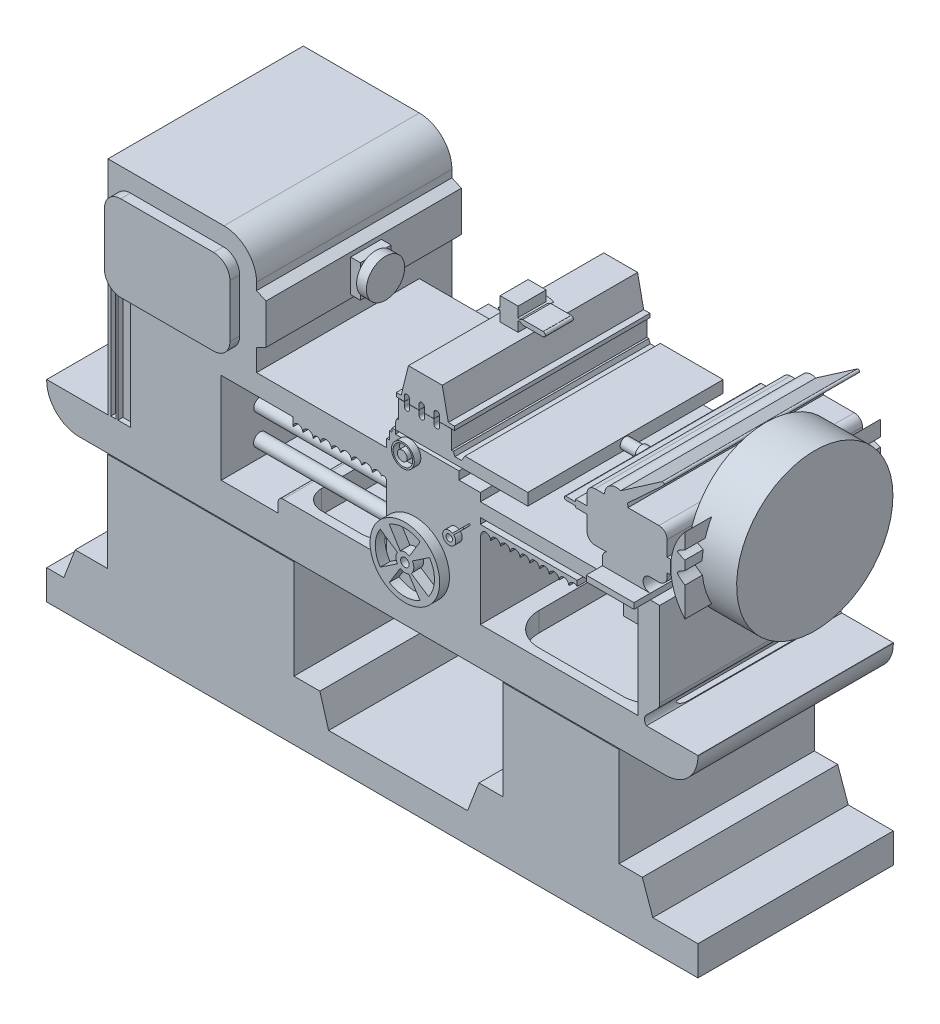
SolidWorks part; units mm, degrees
ref_plane "Front Plane" through (0, 0, 0) normal (0, 0, 1) x (1, 0, 0)
ref_plane "Top Plane" through (0, 0, 0) normal (0, 1, 0) x (1, 0, 0)
ref_plane "Right Plane" through (0, 0, 0) normal (1, 0, 0) x (0, 0, -1)
sketch "Sketch1" plane through (0, 0, 0) normal (0, 0, 1) x (1, 0, 0)
  line L0 (0, 100.2969) -> (0, -49.7031) construction
  line L1 (0, 25.2969) -> (-100, 25.2969) construction
  line L2 (0, 25.2969) -> (100, 25.2969) construction
  line L3 (-94.7329, 25.2969) -> (-91.2441, 34.4213)
  line L4 (-100, 25.2969) -> (100, 25.2969)
  line L5 (-100, 25.2969) -> (-100, 16.1725)
  line L6 (-100, 16.1725) -> (100, 16.1725)
  line L7 (100, 25.2969) -> (100, 16.1725)
  line L8 (-91.2441, 34.4213) -> (-16.1019, 34.4213)
  line L9 (-16.1019, 34.4213) -> (-13.4183, 25.2969)
  line L10 (-13.4183, 25.2969) -> (-94.7329, 25.2969)
  line L11 (29.2518, 25.2969) -> (32.7405, 34.4213)
  line L12 (32.7405, 34.4213) -> (82.9248, 34.4213)
  line L13 (82.9248, 34.4213) -> (86.1452, 25.2969)
  line L14 (86.1452, 25.2969) -> (29.2518, 25.2969)
extrude "Boss-Extrude5" add sketch "Sketch1" against normal blind 60 contours L7 L4 L5 L6 | L9 L8 L3 L4 | L12 L13 L14 L11 region at (0, 20.7347, 0) region at (-53.8769, 29.7991, 0)
sketch "Sketch5" plane through (0, 0, 0) normal (0, 0, 1) x (1, 0, 0)
  line L0 (-91.2441, 34.4213) -> (-16.1019, 34.4213) construction
  line L1 (-81.2902, 34.4213) -> (-24.0553, 34.4213)
  line L2 (-81.2902, 34.4213) -> (-81.2902, 64.836)
  line L3 (-81.2902, 64.836) -> (-24.0553, 64.836)
  line L4 (-24.0553, 34.4213) -> (-24.0553, 64.836)
  line L5 (32.7405, 34.4213) -> (82.9248, 34.4213) construction
  line L6 (40.0921, 34.4213) -> (75.7603, 34.4213)
  line L7 (40.0921, 34.4213) -> (40.0921, 64.836)
  line L8 (40.0921, 64.836) -> (75.7603, 64.836)
  line L9 (75.7603, 34.4213) -> (75.7603, 64.836)
extrude "Boss-Extrude6" add sketch "Sketch5" against normal blind 60
sketch "Sketch6" plane through (0, 0, 0) normal (0, 0, 1) x (1, 0, 0)
  line L0 (-90, 65.1125) -> (90, 65.1125)
  line L1 (100, 75.1125) -> (100, 75.3429)
  line L2 (100, 75.3429) -> (-100, 75.3429)
  line L3 (-100, 75.3429) -> (-100, 75.1125)
  arc A0 (100, 75.1125) -> (90, 65.1125) centre (90, 75.1125) cw
  arc A1 (-90, 65.1125) -> (-100, 75.1125) centre (-90, 75.1125) cw
  dimension "D1" = 10
extrude "Boss-Extrude7" add sketch "Sketch6" against normal blind 60 separate body
sketch "Sketch7" plane through (0, 0, 0) normal (0, 0, 1) x (1, 0, 0)
  line L0 (100, 75.3429) -> (-100, 75.3429) construction
  line L1 (-81.1767, 75.3429) -> (-35.5534, 75.3429)
  line L2 (-81.1767, 75.3429) -> (-81.1767, 143.4491)
  line L3 (-81.1767, 143.4491) -> (-45.5534, 143.4491)
  line L4 (-35.5534, 75.3429) -> (-35.5534, 133.4491)
  arc A0 (-35.5534, 133.4491) -> (-45.5534, 143.4491) centre (-45.5534, 133.4491) ccw
  dimension "D1" = 10
extrude "Boss-Extrude8" add sketch "Sketch7" against normal blind 60
sketch "Sketch8" plane through (0, 0, 0) normal (0, 0, 1) x (1, 0, 0)
  line L0 (-35.5534, 75.3429) -> (-35.5534, 133.4491) construction
  line L1 (-81.1767, 75.3429) -> (-35.5534, 75.3429)
  line L2 (-81.1767, 75.3429) -> (-81.1767, 109.1187)
  line L3 (-81.1767, 109.1187) -> (-35.5534, 109.1187)
  line L4 (-35.5534, 75.3429) -> (-35.5534, 109.1187)
extrude "Cut-Extrude2" cut sketch "Sketch8" against normal blind 50
sketch "Sketch9" plane through (0, 0, -50) normal (0, 0, 1) x (1, 0, 0)
  line L0 (-35.5534, 109.1187) -> (-81.1767, 109.1187) construction
  line L1 (-81.1767, 75.3429) -> (-77.563, 75.3429)
  line L2 (-81.1767, 75.3429) -> (-81.1767, 109.1187)
  line L3 (-81.1767, 109.1187) -> (-77.563, 109.1187)
  line L4 (-77.563, 75.3429) -> (-77.563, 109.1187)
extrude "Boss-Extrude9" add sketch "Sketch9" along normal blind 50
sketch "Sketch10" plane through (0, 0, -50) normal (0, 0, 1) x (1, 0, 0)
  line L0 (-77.563, 75.3429) -> (-77.563, 109.1187) construction
  line L1 (-77.563, 75.3429) -> (-69.8838, 75.3429)
  line L2 (-77.563, 75.3429) -> (-77.563, 109.1187)
  line L3 (-77.563, 109.1187) -> (-69.8838, 109.1187)
  line L4 (-69.8838, 75.3429) -> (-69.8838, 109.1187)
  line L5 (-77.563, 75.3429) -> (-77.563, 109.1187) construction
  line L6 (-35.5534, 109.1187) -> (-77.563, 109.1187) construction
extrude "Boss-Extrude10" add sketch "Sketch10" along normal blind 50
sketch "Sketch11" plane through (0, 0, -50) normal (0, 0, 1) x (1, 0, 0)
  line L0 (-69.8838, 75.3429) -> (-69.8838, 109.1187) construction
  line L1 (-69.8838, 75.3429) -> (-46.3946, 75.3429)
  line L2 (-69.8838, 75.3429) -> (-69.8838, 103.2464)
  line L3 (-69.8838, 103.2464) -> (-46.3946, 103.2464)
  line L4 (-46.3946, 75.3429) -> (-46.3946, 103.2464)
  line L5 (-69.8838, 75.3429) -> (-69.8838, 109.1187) construction
extrude "Boss-Extrude11" add sketch "Sketch11" along normal blind 50
sketch "Sketch12" plane through (0, 0, -50) normal (0, 0, 1) x (1, 0, 0)
  line L1 (-69.8838, 103.2464) -> (5.101, 103.2464)
  line L2 (-69.8838, 103.2464) -> (-69.8838, 109.396)
  line L3 (-69.8838, 109.396) -> (5.101, 109.396)
  line L4 (5.101, 103.2464) -> (5.101, 109.396)
extrude "Boss-Extrude12" add sketch "Sketch12" along normal blind 50
sketch "Sketch14" plane through (0, 0, 0) normal (0, 0, 1) x (1, 0, 0)
  line L0 (-46.3946, 75.3429) -> (-46.3946, 103.2464) construction
  line L1 (-46.3946, 81.508) -> (-41.7443, 81.508)
  line L2 (-46.3946, 81.508) -> (-46.3946, 88.0915)
  line L3 (-46.3946, 88.0915) -> (-41.7443, 88.0915)
  line L4 (-41.7443, 81.508) -> (-41.7443, 88.0915)
  line L6 (-46.3946, 90.9384) -> (-41.7443, 90.9384)
  line L7 (-46.3946, 90.9384) -> (-46.3946, 97.5219)
  line L8 (-46.3946, 97.5219) -> (-41.7443, 97.5219)
  line L9 (-41.7443, 90.9384) -> (-41.7443, 97.5219)
extrude "Boss-Extrude13" add sketch "Sketch14" against normal blind 15
sketch "Sketch15" plane through (0, 0, 0) normal (0, 0, 1) x (1, 0, 0)
  circle A0 centre (-44.0574, 93.9632) radius 1.5
  circle A1 centre (-44.0574, 84.7107) radius 1.5
extrude "Cut-Extrude3" cut sketch "Sketch15" against normal blind 15
sketch "Sketch16" plane through (0, 0, 0) normal (0, 0, 1) x (1, 0, 0)
  line L5 (-80.2963, 75.4754) -> (-78.7823, 75.4754)
  line L6 (-80.2963, 75.4754) -> (-80.2963, 109.396)
  line L7 (-80.2963, 109.396) -> (-78.7823, 109.396)
  line L8 (-78.7823, 75.4754) -> (-78.7823, 109.396)
extrude "Cut-Extrude5" cut sketch "Sketch16" against normal blind 1.5
sketch "Sketch17" plane through (0, 0, 0) normal (0, 0, 1) x (1, 0, 0)
  line L1 (-78.1095, 75.4754) -> (-74.3247, 75.4754)
  line L2 (-78.1095, 75.4754) -> (-78.1095, 109.202)
  line L3 (-78.1095, 109.202) -> (-74.3247, 109.202)
  line L4 (-74.3247, 75.4754) -> (-74.3247, 109.202)
extrude "Cut-Extrude6" cut sketch "Sketch17" against normal blind 1.5
sketch "Sketch18" plane through (0, 0, 0) normal (0, 0, 1) x (1, 0, 0)
  line L0 (-35.5534, 131.2028) -> (-32.652, 129.8906)
  line L1 (-35.5534, 109.396) -> (-35.5534, 133.4491) construction
  line L2 (-32.652, 129.8906) -> (-32.652, 117.5558)
  line L3 (-32.652, 117.5558) -> (-35.5534, 116.1124)
  line L4 (-35.5534, 116.1124) -> (-35.5534, 131.2028)
extrude "Boss-Extrude14" add sketch "Sketch18" against normal blind 60
sketch "Sketch19" plane through (-32.652, 0, 0) normal (1, 0, 0) x (0, 0, -1)
  line L1 (25.9818, 118.6056) -> (35.4297, 118.6056)
  line L2 (25.9818, 118.6056) -> (25.9818, 128.5784)
  line L3 (25.9818, 128.5784) -> (35.4297, 128.5784)
  line L4 (35.4297, 118.6056) -> (35.4297, 128.5784)
extrude "Boss-Extrude15" add sketch "Sketch19" along normal blind 3
sketch "Sketch20" plane through (-29.652, 0, 0) normal (1, 0, 0) x (0, 0, -1)
  circle A1 centre (30.7057, 123.592) radius 5.879
extrude "Boss-Extrude16" add sketch "Sketch20" along normal blind 3
sketch "Sketch22" plane through (0, 0, 0) normal (0, 0, 1) x (1, 0, 0)
  line L0 (100, 75.3429) -> (-46.3946, 75.3429) construction
  line L1 (-28.9192, 75.3429) -> (41.2156, 75.3429)
  line L2 (-28.9192, 75.3429) -> (-28.9192, 78.3108)
  line L3 (-27.4192, 79.8108) -> (39.7156, 79.8108)
  line L4 (41.2156, 75.3429) -> (41.2156, 78.3108)
  arc A0 (41.2156, 78.3108) -> (39.7156, 79.8108) centre (39.7156, 78.3108) ccw
  arc A1 (-28.9192, 78.3108) -> (-27.4192, 79.8108) centre (-27.4192, 78.3108) cw
  dimension "D1" = 1.5
extrude "Boss-Extrude17" add sketch "Sketch22" against normal blind 60
sketch "Sketch23" plane through (0, 0, 0) normal (0, 0, 1) x (1, 0, 0)
  line L0 (39.7156, 79.8108) -> (-27.4192, 79.8108) construction
  line L1 (4.424, 111.8845) -> (33.1797, 111.8845)
  line L2 (4.424, 111.8845) -> (4.424, 79.8108)
  line L3 (4.424, 79.8108) -> (30.6797, 79.8108)
  line L4 (33.1797, 111.8845) -> (33.1797, 82.3108)
  arc A0 (30.6797, 79.8108) -> (33.1797, 82.3108) centre (30.6797, 82.3108) ccw
  point P8 (33.1797, 79.8108)
  dimension "D1" = 2.5
extrude "Boss-Extrude18" add sketch "Sketch23" against normal blind 60
sketch "Sketch24" plane through (0, 0, 0) normal (0, 0, 1) x (1, 0, 0)
  line L0 (33.1797, 111.8845) -> (4.424, 111.8845) construction
  circle A0 centre (11.391, 111.8845) radius 3.5
  circle A1 centre (11.391, 111.8845) radius 3
extrude "Boss-Extrude19" add sketch "Sketch24" along normal blind 2
sketch "Sketch25" plane through (0, 0, 0) normal (0, 0, 1) x (1, 0, 0)
  line L0 (14.391, 111.8845) -> (8.391, 111.8845) construction
  circle A0 centre (11.391, 111.8845) radius 1.5
extrude "Boss-Extrude20" add sketch "Sketch25" along normal blind 2.2
sketch "Sketch26" plane through (0, 0, 0) normal (0, 0, 1) x (1, 0, 0)
  circle A0 centre (25.6121, 97.0651) radius 2
  circle A1 centre (25.6121, 97.0651) radius 1
extrude "Boss-Extrude21" add sketch "Sketch26" along normal blind 2
sketch "Sketch27" plane through (0, 0, 2) normal (0, 0, 1) x (1, 0, 0)
  line L0 (26.6357, 98.7833) -> (29.6928, 101.8405)
  line L1 (29.6928, 101.8405) -> (30.0087, 101.5246)
  line L2 (30.0087, 101.5246) -> (27.0162, 98.4893)
  line L3 (27.0162, 98.4893) -> (26.6357, 98.7833)
  circle A0 centre (25.6121, 97.0651) radius 2 construction
  circle A1 centre (25.6121, 97.0651) radius 2 construction
extrude "Boss-Extrude22" add sketch "Sketch27" against normal blind 2
sketch "Sketch28" plane through (0, 0, 2) normal (0, 0, 1) x (1, 0, 0)
  line L0 (30.0087, 101.5246) -> (29.6928, 101.8405) construction
  circle A0 centre (29.8508, 101.6825) radius 0.202
extrude "Boss-Extrude23" add sketch "Sketch28" against normal blind 2
sketch "Sketch29" plane through (0, 0, 0) normal (0, 0, 1) x (1, 0, 0)
  line L2 (8.2077, 92.4495) -> (11.5486, 87.0494)
  line L3 (5.4261, 89.7621) -> (10.708, 86.2373)
  line L4 (14.2109, 82.2439) -> (17.6705, 76.9035)
  line L5 (14.9295, 82.7559) -> (20.2667, 79.2392)
  line L6 (17.6705, 92.518) -> (14.4082, 87.0701)
  line L7 (20.5646, 89.7621) -> (15.2828, 86.2373)
  line L8 (5.4261, 79.6594) -> (10.708, 83.1842)
  line L9 (8.2077, 76.972) -> (11.5486, 82.3721)
  line L11 (14.9399, 82.7662) -> (14.9902, 82.7159)
  circle A0 centre (12.9954, 84.7107) radius 10.7
  arc A1 (8.2077, 76.972) -> (17.6705, 76.9035) centre (12.9954, 84.7107) ccw
  circle A2 centre (12.9954, 84.7107) radius 2.75
  circle A3 centre (12.9954, 84.7107) radius 1.3
  arc A4 (20.2667, 79.2392) -> (20.5646, 89.7621) centre (12.9954, 84.7107) ccw
  arc A5 (17.6705, 92.518) -> (8.2077, 92.4495) centre (12.9954, 84.7107) ccw
  arc A6 (5.4261, 89.7621) -> (5.4261, 79.6594) centre (12.9954, 84.7107) ccw
  point P8 (12.9954, 84.7107)
  point P11 (12.9954, 84.7107)
extrude "Boss-Extrude24" add sketch "Sketch29" along normal blind 3 contours A0 A6 L3 A2 L2 A5 L6 L7 A4 L5 L4 A1 L9 L8 | A2 A3 region at (12.976, 87.3829, 0) region at (2.598, 84.7107, 0)
sketch "Sketch30" plane through (0, 0, 0) normal (0, 0, 1) x (1, 0, 0)
  line L0 (33.1797, 109.396) -> (88.265, 109.396)
  line L1 (33.1797, 82.3108) -> (33.1797, 111.8845) construction
  line L2 (88.265, 109.396) -> (88.265, 83.3463)
  line L5 (100, 75.3429) -> (41.2156, 75.3429) construction
  line L6 (84.1725, 75.3429) -> (41.2156, 75.3429)
  line L9 (33.1797, 82.3108) -> (33.1797, 109.396)
  line L10 (41.2156, 75.3429) -> (41.2156, 78.3108)
  line L17 (30.6797, 79.8108) -> (39.7156, 79.8108)
  line L18 (84.1725, 78.2184) -> (87.5327, 81.5786)
  arc A0 (84.1725, 78.2184) -> (84.1725, 75.3429) centre (85.6103, 76.7806) ccw
  arc A1 (87.5327, 81.5786) -> (88.265, 83.3463) centre (85.765, 83.3463) ccw
  arc A6 (39.7156, 79.8108) -> (41.2156, 78.3108) centre (39.7156, 78.3108) cw
  arc A7 (30.6797, 79.8108) -> (33.1797, 82.3108) centre (30.6797, 82.3108) ccw
  dimension "D1" = 2.5
extrude "Boss-Extrude25" add sketch "Sketch30" against normal blind 60
sketch "Sketch33" plane through (-41.7443, 0, 0) normal (1, 0, 0) x (0, 0, -1)
  circle A0 centre (7.3545, 94.1808) radius 2
  circle A1 centre (7.2829, 84.8797) radius 2
extrude "Boss-Extrude26" add sketch "Sketch33" along normal blind 46
sketch "Sketch34" plane through (0, 0, 0) normal (0, 0, 1) x (1, 0, 0)
  line L0 (-46.3946, 103.2464) -> (4.424, 103.2464) construction
  line L1 (-24.3452, 103.2464) -> (4.424, 103.2464)
  line L2 (-24.3452, 103.2464) -> (-24.3452, 100.5835)
  line L4 (4.424, 103.2464) -> (4.424, 100.5835)
  line L5 (4.424, 103.2464) -> (4.424, 91.1155) construction
  arc A0 (-21.3272, 100.5835) -> (-24.3452, 100.5835) centre (-22.8362, 100.5835) ccw
  arc A1 (-18.1779, 100.5835) -> (-21.3272, 100.5835) centre (-19.7525, 100.5835) ccw
  arc A4 (-12.5353, 100.5835) -> (-15.9471, 100.5835) centre (-14.2412, 100.5835) ccw
  arc A5 (-9.7198, 101.0316) -> (-12.5353, 100.5835) centre (-11.0919, 100.5835) ccw
  arc A6 (-6.368, 100.5835) -> (-9.7198, 101.0316) centre (-8.0738, 100.5835) ccw
  arc A7 (-3.2541, 100.9157) -> (-6.368, 100.5835) centre (-4.7933, 100.5835) ccw
  arc A8 (0, 100.5835) -> (-3.2541, 100.9157) centre (-1.644, 100.5835) ccw
  arc A9 (2.8069, 101.061) -> (0, 100.5835) centre (1.4441, 100.5835) ccw
  arc A10 (4.424, 100.5835) -> (2.8069, 101.061) centre (3.5449, 100.5835) ccw
  arc A11 (-18.1779, 100.5835) -> (-15.9471, 100.5835) centre (-17.0625, 100.5835) cw
extrude "Boss-Extrude27" add sketch "Sketch34" against normal blind 60
sketch "Sketch35" plane through (0, 0, 0) normal (0, 0, 1) x (1, 0, 0)
  line L1 (33.1797, 76.7693) -> (81.5667, 76.7693)
  line L2 (33.1797, 76.7693) -> (33.1797, 105.2485)
  line L3 (33.1797, 105.2485) -> (81.5667, 105.2485)
  line L4 (81.5667, 76.7693) -> (81.5667, 105.2485)
extrude "Cut-Extrude7" cut sketch "Sketch35" against normal blind 50
sketch "Sketch36" plane through (81.5667, 0, 0) normal (-1, 0, 0) x (0, 0, 1)
  line L1 (-25.0843, 103.0373) -> (-11.8771, 103.0373)
  line L2 (-25.0843, 103.0373) -> (-25.0843, 79.5831)
  line L3 (-25.0843, 79.5831) -> (-11.8771, 79.5831)
  line L4 (-11.8771, 103.0373) -> (-11.8771, 79.5831)
extrude "Boss-Extrude28" add sketch "Sketch36" along normal blind 10
sketch "Sketch37" plane through (0, 0, 0) normal (0, 0, 1) x (1, 0, 0)
  line L0 (33.1797, 105.2485) -> (33.1797, 76.7693) construction
  line L1 (33.1797, 103.3985) -> (62.9121, 103.3985)
  line L2 (33.1797, 103.3985) -> (33.1797, 100.6757)
  line L3 (33.1797, 100.6757) -> (33.356, 100.6757)
  line L4 (62.9121, 103.3985) -> (62.9121, 101.7278)
  line L5 (60.3452, 100.6757) -> (60.356, 100.6757)
  line L6 (57.3452, 100.6757) -> (57.356, 100.6757)
  line L7 (54.3452, 100.6757) -> (54.356, 100.6757)
  line L8 (51.3452, 100.6757) -> (51.356, 100.6757)
  line L9 (48.3452, 100.6757) -> (48.356, 100.6757)
  line L10 (45.3452, 100.6757) -> (45.356, 100.6757)
  line L11 (42.3452, 100.6757) -> (42.356, 100.6757)
  line L12 (39.3452, 100.6757) -> (39.356, 100.6757)
  line L13 (36.3452, 100.6757) -> (36.356, 100.6757)
  arc A1 (36.3452, 100.6757) -> (33.356, 100.6757) centre (34.8506, 100.6757) ccw
  arc A2 (39.3452, 100.6757) -> (36.356, 100.6757) centre (37.8506, 100.6757) ccw
  arc A3 (42.3452, 100.6757) -> (39.356, 100.6757) centre (40.8506, 100.6757) ccw
  arc A4 (45.3452, 100.6757) -> (42.356, 100.6757) centre (43.8506, 100.6757) ccw
  arc A5 (48.3452, 100.6757) -> (45.356, 100.6757) centre (46.8506, 100.6757) ccw
  arc A6 (51.3452, 100.6757) -> (48.356, 100.6757) centre (49.8506, 100.6757) ccw
  arc A7 (54.3452, 100.6757) -> (51.356, 100.6757) centre (52.8506, 100.6757) ccw
  arc A8 (57.3452, 100.6757) -> (54.356, 100.6757) centre (55.8506, 100.6757) ccw
  arc A9 (60.3452, 100.6757) -> (57.356, 100.6757) centre (58.8506, 100.6757) ccw
  arc A10 (62.9121, 101.7278) -> (60.356, 100.6757) centre (61.8506, 100.6757) ccw
extrude "Boss-Extrude29" add sketch "Sketch37" against normal blind 60
sketch "Sketch38" plane through (0, 0, -50) normal (0, 0, 1) x (1, 0, 0)
  line L0 (81.5667, 76.7693) -> (81.5667, 105.2485) construction
  line L1 (33.1797, 76.7693) -> (81.5667, 76.7693)
  line L2 (33.1797, 76.7693) -> (33.1797, 105.2485)
  line L3 (33.1797, 105.2485) -> (81.5667, 105.2485)
  line L4 (81.5667, 76.7693) -> (81.5667, 105.2485)
  line L5 (81.5667, 76.7693) -> (81.5667, 105.2485) construction
extrude "Cut-Extrude8" cut sketch "Sketch38" against normal blind 60
sketch "Sketch39" plane through (0, 76.7693, 0) normal (0, 1, 0) x (1, 0, 0)
  line L1 (48.4331, 2.7857) -> (74.0552, 2.7857)
  line L2 (38.4331, 12.7857) -> (38.4331, 46.7027)
  line L3 (48.4331, 56.7027) -> (74.0552, 56.7027)
  line L4 (84.0552, 12.7857) -> (84.0552, 46.7027)
  arc A0 (48.4331, 2.7857) -> (38.4331, 12.7857) centre (48.4331, 12.7857) cw
  arc A1 (74.0552, 2.7857) -> (84.0552, 12.7857) centre (74.0552, 12.7857) ccw
  arc A2 (84.0552, 46.7027) -> (74.0552, 56.7027) centre (74.0552, 46.7027) ccw
  arc A3 (48.4331, 56.7027) -> (38.4331, 46.7027) centre (48.4331, 46.7027) ccw
  dimension "D1" = 10
extrude "Cut-Extrude9" cut sketch "Sketch39" against normal blind 6
sketch "Sketch42" plane through (0, 0, 0) normal (0, 0, 1) x (1, 0, 0)
  line L25 (-46.3946, 81.508) -> (-41.7443, 81.508)
  line L26 (-46.3946, 81.508) -> (-46.3946, 88.0915)
  line L27 (-46.3946, 88.0915) -> (-41.7443, 88.0915)
  line L28 (-41.7443, 81.508) -> (-41.7443, 88.0915)
  line L33 (-46.3946, 90.9384) -> (-41.7443, 90.9384)
  line L34 (-46.3946, 90.9384) -> (-46.3946, 97.5219)
  line L35 (-46.3946, 97.5219) -> (-41.7443, 97.5219)
  line L36 (-41.7443, 90.9384) -> (-41.7443, 97.5219)
extrude "Cut-Extrude10" cut sketch "Sketch42" against normal blind 20
sketch "Sketch44" plane through (-46.3946, 0, 0) normal (1, 0, 0) x (0, 0, -1)
  line L0 (-65.065, 97.5722) -> (-65.065, 83.6819) construction
  line L1 (11.4217, 90.0578) -> (18.0253, 90.0578)
  line L2 (11.4217, 90.0578) -> (11.4217, 97.5722)
  line L3 (11.4217, 97.5722) -> (18.0253, 97.5722)
  line L4 (18.0253, 90.0578) -> (18.0253, 97.5722)
  line L5 (23.2627, 90.0578) -> (30, 90.0578)
  line L6 (23.2627, 90.0578) -> (23.2627, 97.5722)
  line L7 (23.2627, 97.5722) -> (30, 97.5722)
  line L8 (30, 90.0578) -> (30, 97.5722)
extrude "Boss-Extrude30" add sketch "Sketch44" along normal blind 5
sketch "Sketch45" plane through (-41.3946, 0, 0) normal (1, 0, 0) x (0, 0, -1)
  circle A0 centre (14.62, 93.5216) radius 1.45
  circle A1 centre (25.5987, 93.5216) radius 1.45
extrude "Boss-Extrude31" add sketch "Sketch45" along normal blind 120
sketch "Sketch46" plane through (71.5667, 0, 0) normal (-1, 0, 0) x (0, 0, 1)
  line L1 (-16.2036, 90.5132) -> (-10.5109, 90.5132)
  line L2 (-16.2036, 90.5132) -> (-16.2036, 97.5722)
  line L3 (-16.2036, 97.5722) -> (-10.5109, 97.5722)
  line L4 (-10.5109, 90.5132) -> (-10.5109, 97.5722)
  line L5 (-30.3217, 90.5132) -> (-24.6289, 90.5132)
  line L6 (-30.3217, 90.5132) -> (-30.3217, 97.5722)
  line L7 (-30.3217, 97.5722) -> (-24.6289, 97.5722)
  line L8 (-24.6289, 90.5132) -> (-24.6289, 97.5722)
extrude "Boss-Extrude32" add sketch "Sketch46" along normal blind 5
sketch "Sketch48" plane through (0, 0, -25.0843) normal (0, 0, -1) x (-1, 0, 0)
  line L6 (-71.5667, 79.5831) -> (-81.5667, 79.5831) construction
  line L7 (-81.5667, 79.5831) -> (-71.5667, 79.5831)
  line L8 (-81.5667, 79.5831) -> (-81.5667, 103.0373)
  line L9 (-81.5667, 103.0373) -> (-71.5667, 103.0373)
  line L10 (-71.5667, 79.5831) -> (-71.5667, 103.0373)
extrude "Boss-Extrude33" add sketch "Sketch48" along normal blind 7
sketch "Sketch49" plane through (0, 79.8108, 0) normal (0, 1, 0) x (1, 0, 0)
  line L0 (-24.3452, 60) -> (-24.3452, 50) construction
  line L1 (-18.3452, 58.0852) -> (-6, 58.0852)
  line L2 (-24.3452, 52.0852) -> (-24.3452, 8.7857)
  line L3 (-18.3452, 2.7857) -> (-6, 2.7857)
  line L4 (0, 52.0852) -> (0, 8.7857)
  arc A0 (-24.3452, 52.0852) -> (-18.3452, 58.0852) centre (-18.3452, 52.0852) cw
  arc A1 (0, 52.0852) -> (-6, 58.0852) centre (-6, 52.0852) ccw
  arc A2 (-6, 2.7857) -> (0, 8.7857) centre (-6, 8.7857) ccw
  arc A3 (-18.3452, 2.7857) -> (-24.3452, 8.7857) centre (-18.3452, 8.7857) cw
  point P8 (-24.3452, 58.0852)
  dimension "D1" = 6
extrude "Cut-Extrude12" cut sketch "Sketch49" against normal blind 7
sketch "Sketch50" plane through (0, 0, 0) normal (0, 0, 1) x (1, 0, 0)
  line L5 (-74.2636, 111.5249) -> (-45.7426, 111.5249)
  line L6 (-79.2636, 116.5249) -> (-79.2636, 132.7827)
  line L7 (-74.2636, 137.7827) -> (-45.7426, 137.7827)
  line L8 (-40.7426, 116.5249) -> (-40.7426, 132.7827)
  arc A1 (-45.7426, 111.5249) -> (-40.7426, 116.5249) centre (-45.7426, 116.5249) ccw
  arc A2 (-74.2636, 111.5249) -> (-79.2636, 116.5249) centre (-74.2636, 116.5249) cw
  arc A3 (-40.7426, 132.7827) -> (-45.7426, 137.7827) centre (-45.7426, 132.7827) ccw
  arc A4 (-74.2636, 137.7827) -> (-79.2636, 132.7827) centre (-74.2636, 132.7827) ccw
  dimension "D1" = 5
extrude "Boss-Extrude34" add sketch "Sketch50" along normal blind 3
sketch "Sketch51" plane through (0, 0, -60) normal (0, 0, -1) x (-1, 0, 0)
  line L0 (26.652, 123.592) -> (-112.2579, 123.592) construction
  line L1 (26.652, 129.471) -> (26.652, 117.713) construction
  line L2 (-33.1797, 111.8845) -> (-4.424, 111.8845) construction
  line L3 (-25.4378, 111.8845) -> (-6.0829, 111.8845)
  line L4 (-25.4378, 111.8845) -> (-25.4378, 112.5435)
  line L5 (-24.4378, 113.5435) -> (-7.0829, 113.5435)
  line L6 (-6.0829, 111.8845) -> (-6.0829, 112.5435)
  arc A0 (-6.0829, 112.5435) -> (-7.0829, 113.5435) centre (-7.0829, 112.5435) ccw
  arc A1 (-25.4378, 112.5435) -> (-24.4378, 113.5435) centre (-24.4378, 112.5435) cw
  dimension "D1" = 1
extrude "Boss-Extrude35" add sketch "Sketch51" against normal blind 60
sketch "Sketch52" plane through (0, 0, -60) normal (0, 0, -1) x (-1, 0, 0)
  line L0 (26.652, 123.592) -> (-92.303, 123.592) construction
  line L1 (26.652, 129.471) -> (26.652, 117.713) construction
sketch "Sketch60" plane through (0, 0, 0) normal (0, 0, 1) x (1, 0, 0)
  line L0 (6.0829, 111.8845) -> (4.424, 111.8845) construction
  line L1 (5.2534, 111.8845) -> (26.5758, 111.8845)
  line L2 (5.2534, 111.8845) -> (5.2534, 114.3372)
  line L3 (5.2534, 114.3372) -> (26.5758, 114.3372)
  line L4 (26.5758, 111.8845) -> (26.5758, 114.3372)
extrude "Boss-Extrude44" add sketch "Sketch60" against normal blind 60
sketch "Sketch61" plane through (0, 0, 0) normal (0, 0, 1) x (1, 0, 0)
  line L0 (8.8943, 114.3372) -> (5.2534, 114.3372) construction
  line L2 (7.0738, 114.3372) -> (7.0738, 117.5182)
  line L3 (28.4576, 119.1929) -> (47.7477, 119.1929)
  line L4 (47.7477, 115.5334) -> (47.7477, 119.1929)
  line L5 (7.0738, 115.5334) -> (47.7477, 115.5334)
  line L6 (7.0738, 117.5182) -> (27.4108, 117.5182)
  line L7 (27.4108, 117.5182) -> (28.4576, 119.1929)
extrude "Boss-Extrude48" add sketch "Sketch61" against normal blind 60 separate body contours L7 L6 L2 L5 L4 L3 region at (30.4483, 117.0566, 0)
sketch "Sketch65" plane through (0, 0, 0) normal (0, 0, 1) x (1, 0, 0)
  line L0 (8.8943, 114.3372) -> (5.2534, 114.3372) construction
  line L1 (7.0738, 115.5334) -> (6.0948, 115.5334)
  line L2 (7.0738, 115.5334) -> (7.0738, 114.3372)
  line L3 (7.0738, 114.3372) -> (6.0948, 114.3372)
  line L4 (6.0948, 115.5334) -> (6.0948, 114.3372)
extrude "Boss-Extrude49" add sketch "Sketch65" against normal blind 60
sketch "Sketch66" plane through (0, 0, 0) normal (0, 0, 1) x (1, 0, 0)
  line L0 (24.8676, 118.6967) -> (25.385, 117.5182)
  line L1 (7.0738, 117.5182) -> (25.385, 117.5182)
  line L3 (7.54, 118.6967) -> (24.8676, 118.6967)
  line L5 (7.54, 118.6967) -> (7.0738, 117.5182)
extrude "Boss-Extrude51" add sketch "Sketch66" against normal blind 60
sketch "Sketch67" plane through (0, 0, 0) normal (0, 0, 1) x (1, 0, 0)
  line L0 (24.8676, 118.6967) -> (7.54, 118.6967) construction
  line L1 (8.1002, 118.6967) -> (24.2891, 118.6967)
  line L2 (8.1002, 118.6967) -> (8.1002, 124.3411)
  line L3 (8.1002, 124.3411) -> (24.2891, 124.3411)
  line L4 (24.2891, 118.6967) -> (24.2891, 124.3411)
extrude "Boss-Extrude52" add sketch "Sketch67" against normal blind 60
sketch "Sketch68" plane through (0, 0, 0) normal (0, 0, 1) x (1, 0, 0)
  line L1 (7.3816, 124.4031) -> (25.2451, 124.4031)
  line L2 (7.3816, 124.4031) -> (7.3816, 125.5816)
  line L3 (7.3816, 125.5816) -> (25.2451, 125.5816)
  line L4 (25.2451, 124.4031) -> (25.2451, 125.5816)
extrude "Boss-Extrude53" add sketch "Sketch68" against normal blind 60 separate body
sketch "Sketch69" plane through (0, 0, 0) normal (0, 0, 1) x (1, 0, 0)
  line L0 (8.8618, 125.5816) -> (23.3346, 125.5816)
  line L1 (25.2451, 125.5816) -> (7.3816, 125.5816) construction
  line L2 (23.3346, 125.5816) -> (21.4738, 134.5638)
  line L3 (21.4738, 134.5638) -> (11.0844, 134.5638)
  line L4 (11.0844, 134.5638) -> (8.8618, 125.5816)
extrude "Boss-Extrude54" add sketch "Sketch69" against normal blind 60
sketch "Sketch72" plane through (0, 134.5638, 0) normal (0, 1, 0) x (1, 0, 0)
  line L1 (19.0783, 25.6936) -> (13.5484, 25.6936)
  line L2 (19.0783, 25.6936) -> (19.0783, 34.3064)
  line L3 (19.0783, 34.3064) -> (13.5484, 34.3064)
  line L4 (13.5484, 25.6936) -> (13.5484, 34.3064)
  line L5 (19.0783, 25.6936) -> (13.5484, 34.3064) construction
  line L6 (19.0783, 34.3064) -> (13.5484, 25.6936) construction
  point P0 (16.3133, 30)
extrude "Boss-Extrude55" add sketch "Sketch72" along normal blind 7
sketch "Sketch74" plane through (0, 0, -25.6936) normal (0, 0, 1) x (1, 0, 0)
  line L0 (19.0783, 138.0638) -> (20.4563, 138.6631)
  line L1 (19.0783, 141.5638) -> (19.0783, 134.5638) construction
  line L2 (20.4563, 138.6631) -> (26.7806, 138.6631)
  line L3 (26.7806, 138.6631) -> (26.7806, 138.6101)
  line L4 (26.7806, 137.2145) -> (20.4563, 137.2145)
  line L5 (20.4563, 137.2145) -> (19.0783, 138.0638)
  line L6 (26.7806, 137.2675) -> (26.7806, 137.2145)
  arc A0 (26.7806, 137.2675) -> (26.7806, 138.6101) centre (26.7806, 137.9388) ccw
extrude "Boss-Extrude57" add sketch "Sketch74" against normal blind 8.6 separate body
sketch "Sketch76" plane through (0, 0, -25.6936) normal (0, 0, 1) x (1, 0, 0)
  ellipse E0 centre (16.4275, 138.0427) end of major axis (19.9029, 138.0427) minor radius 0.6373
extrude "Boss-Extrude59" add sketch "Sketch76" against normal blind 10
sketch "Sketch77" plane through (0, 0, 0) normal (0, 0, 1) x (1, 0, 0)
  line L0 (10.6128, 125.9865) -> (10.6128, 123.0432) construction
  line L1 (11.3937, 125.9865) -> (11.3937, 123.0432)
  line L2 (9.8319, 125.9865) -> (9.8319, 123.0432)
  line L3 (15.178, 125.9865) -> (15.178, 123.0432) construction
  line L4 (16.019, 125.9865) -> (16.019, 123.0432)
  line L5 (14.3371, 125.9865) -> (14.3371, 123.0432)
  line L6 (19.8033, 125.9865) -> (19.8033, 123.0432) construction
  line L7 (20.7044, 125.9865) -> (20.7044, 123.0432)
  line L8 (18.9023, 125.9865) -> (18.9023, 123.0432)
  arc A0 (11.3937, 125.9865) -> (9.8319, 125.9865) centre (10.6128, 125.9865) ccw
  arc A1 (9.8319, 123.0432) -> (11.3937, 123.0432) centre (10.6128, 123.0432) ccw
  arc A2 (16.019, 125.9865) -> (14.3371, 125.9865) centre (15.178, 125.9865) ccw
  arc A3 (14.3371, 123.0432) -> (16.019, 123.0432) centre (15.178, 123.0432) ccw
  arc A4 (20.7044, 125.9865) -> (18.9023, 125.9865) centre (19.8033, 125.9865) ccw
  arc A5 (18.9023, 123.0432) -> (20.7044, 123.0432) centre (19.8033, 123.0432) ccw
  point P2 (10.6128, 124.5148)
  point P7 (15.178, 124.5148)
  point P14 (19.8033, 124.5148)
extrude "Cut-Extrude13" cut sketch "Sketch77" against normal blind 60
sketch "Sketch78" plane through (47.7477, 0, 0) normal (1, 0, 0) x (0, 0, -1)
  circle A1 centre (30, 117.3628) radius 1.2737
  circle A2 centre (30, 117.3628) radius 1.6332
extrude "Boss-Extrude60" add sketch "Sketch78" along normal blind 5
sketch "Sketch79" plane through (52.7477, 0, 0) normal (1, 0, 0) x (0, 0, -1)
  circle A0 centre (30, 117.3628) radius 2.0331
extrude "Boss-Extrude61" add sketch "Sketch79" along normal blind 2
sketch "Sketch80" plane through (54.7477, 0, 0) normal (1, 0, 0) x (0, 0, -1)
  circle A0 centre (30, 118.7505) radius 0.5
extrude "Boss-Extrude62" add sketch "Sketch80" along normal blind 5
sketch "Sketch81" plane through (54.7477, 0, 0) normal (1, 0, 0) x (0, 0, -1)
  circle A0 centre (30, 117.3628) radius 1.4264
extrude "Cut-Extrude14" cut sketch "Sketch81" against normal blind 1
sketch "Sketch84" plane through (0, 0, 0) normal (0, 0, 1) x (1, 0, 0)
  line L0 (88.265, 109.396) -> (33.1797, 109.396) construction
  line L1 (70.7024, 109.396) -> (85.3571, 109.396)
  line L2 (70.7024, 109.396) -> (70.7024, 113.5477)
  line L3 (72.7024, 115.5477) -> (85.3571, 115.5477)
  line L4 (85.3571, 109.396) -> (85.3571, 111.1731)
  line L5 (70.7024, 111.1731) -> (85.3571, 111.1731)
  arc A1 (85.3571, 115.5477) -> (85.3571, 111.1731) centre (85.3571, 113.3604) ccw
  arc A2 (72.7024, 115.5477) -> (70.7024, 113.5477) centre (72.7024, 113.5477) ccw
  dimension "D1" = 2
extrude "Boss-Extrude63" add sketch "Sketch84" against normal blind 60 contours L3 A2 L2 L5 A1 | L5 L2 L1 L4 region at (78.0298, 110.2846, 0) region at (77.2729, 113.3336, 0)
sketch "Sketch85" plane through (0, 0, 0) normal (0, 0, 1) x (1, 0, 0)
  line L1 (70.7024, 109.396) -> (85.3571, 109.396)
  line L2 (70.7024, 109.396) -> (70.7024, 111.1731)
  line L3 (70.7024, 111.1731) -> (85.3571, 111.1731)
  line L4 (85.3571, 109.396) -> (85.3571, 111.1731)
extrude "Boss-Extrude64" add sketch "Sketch85" along normal blind 5
sketch "Sketch86" plane through (0, 0, 0) normal (0, 0, 1) x (1, 0, 0)
  line L0 (78.3377, 131.6387) -> (89.4877, 141.9365)
  line L1 (68.4308, 115.46) -> (88.0249, 115.46)
  line L2 (65.9308, 117.96) -> (65.9308, 122.4795)
  line L3 (68.4308, 130.5136) -> (71.3138, 130.5136)
  line L4 (90.5249, 117.96) -> (90.5249, 119.1724)
  line L5 (76.2258, 133.869) -> (88.9162, 142.6277)
  line L6 (-26.652, 123.592) -> (92.303, 123.592) construction
  line L7 (62.4041, 122.4795) -> (65.9308, 122.4795)
  line L8 (62.4041, 122.4795) -> (62.4041, 122.9618)
  line L9 (62.4041, 124.7045) -> (65.9308, 124.7045)
  line L11 (62.4041, 122.4795) -> (65.9308, 124.7045) construction
  line L12 (62.4041, 124.7045) -> (65.9308, 122.4795) construction
  line L13 (59.4676, 122.9724) -> (59.4676, 122.9618)
  line L14 (62.4041, 124.018) -> (59.4676, 124.018)
  line L16 (62.4041, 122.9618) -> (59.4676, 122.9618)
  line L17 (59.4676, 124.018) -> (59.4676, 124.0075)
  line L18 (90.5249, 123.3577) -> (91.6472, 123.3577)
  line L20 (90.5249, 119.1724) -> (91.6472, 119.1724)
  line L21 (91.6472, 123.3577) -> (91.6472, 119.1724)
  line L22 (95.9996, 132.752) -> (95.9996, 128.0136)
  line L23 (95.9996, 132.752) -> (97.0105, 132.752)
  line L24 (95.9996, 132.752) -> (95.9996, 128.0136)
  line L25 (95.9996, 109.6149) -> (97.0105, 109.6149)
  line L26 (97.0105, 132.752) -> (97.0105, 109.6149)
  line L27 (62.4041, 124.018) -> (62.4041, 124.7045)
  line L28 (65.9308, 124.7045) -> (65.9308, 128.0136)
  line L29 (78.518, 130.5136) -> (88.0249, 130.5136)
  line L30 (90.5249, 123.3577) -> (90.5249, 128.0136)
  line L31 (95.9996, 125.3219) -> (95.9996, 122.4977)
  line L32 (95.9996, 125.3219) -> (95.9996, 122.4977)
  line L33 (95.9996, 118.6439) -> (95.9996, 109.6149)
  line L34 (95.9996, 118.6439) -> (95.9996, 109.6149)
  arc A0 (68.4308, 115.46) -> (65.9308, 117.96) centre (68.4308, 117.96) cw
  arc A1 (90.5249, 117.96) -> (88.0249, 115.46) centre (88.0249, 117.96) cw
  arc A2 (88.0249, 130.5136) -> (90.5249, 128.0136) centre (88.0249, 128.0136) cw
  arc A3 (68.4308, 130.5136) -> (65.9308, 128.0136) centre (68.4308, 128.0136) ccw
  arc A4 (78.518, 130.5136) -> (71.3138, 130.5136) centre (74.9159, 130.5136) ccw
  circle A5 centre (89.1539, 142.243) radius 0.4516
  arc A7 (59.4676, 124.0075) -> (59.4676, 122.9724) centre (59.4676, 123.4899) ccw
  arc A8 (91.6472, 121.265) -> (95.9996, 132.752) centre (108.9818, 121.265) cw
  arc A9 (91.6472, 121.265) -> (95.9996, 109.6149) centre (109.4154, 121.265) ccw
  conic Q0 (95.9996, 128.0136) -> (95.9996, 125.3219) control (92.9081, 126.492) rho 0.72973
  conic Q1 (95.9996, 122.4977) -> (95.9996, 118.6439) control (92.9545, 120.8816) rho 0.75
  point P13 (0, 0)
  point P20 (64.1674, 123.592)
  arc M39 (85.3571, 111.1731) -> (85.3571, 115.5477) centre (85.3571, 113.3604) cw
  line M40 (85.3571, 115.5477) -> (72.7024, 115.5477)
  arc M41 (72.7024, 115.5477) -> (70.7024, 113.5477) centre (72.7024, 113.5477) ccw
  dimension "D1" = 2.5
extrude "Boss-Extrude65" add sketch "Sketch86" against normal blind 60 contours L17 A7 L13 L16 L8 L7 L2 A0 L1 A1 L4 L20 L21 L18 L30 A2 L29 A4 L3 A3 L28 L9 L27 L14 M41 M40 M39 | Q1 L31 Q0 L22 A8 A9 L33 | A5 L5 A4 L0 | A5 region at (82.1825, 136.6722, 0) region at (92.992, 127.3236, 0) region at (77.7793, 123.4647, 0) region at (89.1539, 142.243, 0)
sketch "Sketch87" plane through (91.6472, 0, 0) normal (1, 0, 0) x (0, 0, -1)
  circle A0 centre (29.2313, 121.1733) radius 24
extrude "Boss-Extrude66" add sketch "Sketch87" along normal blind 15
